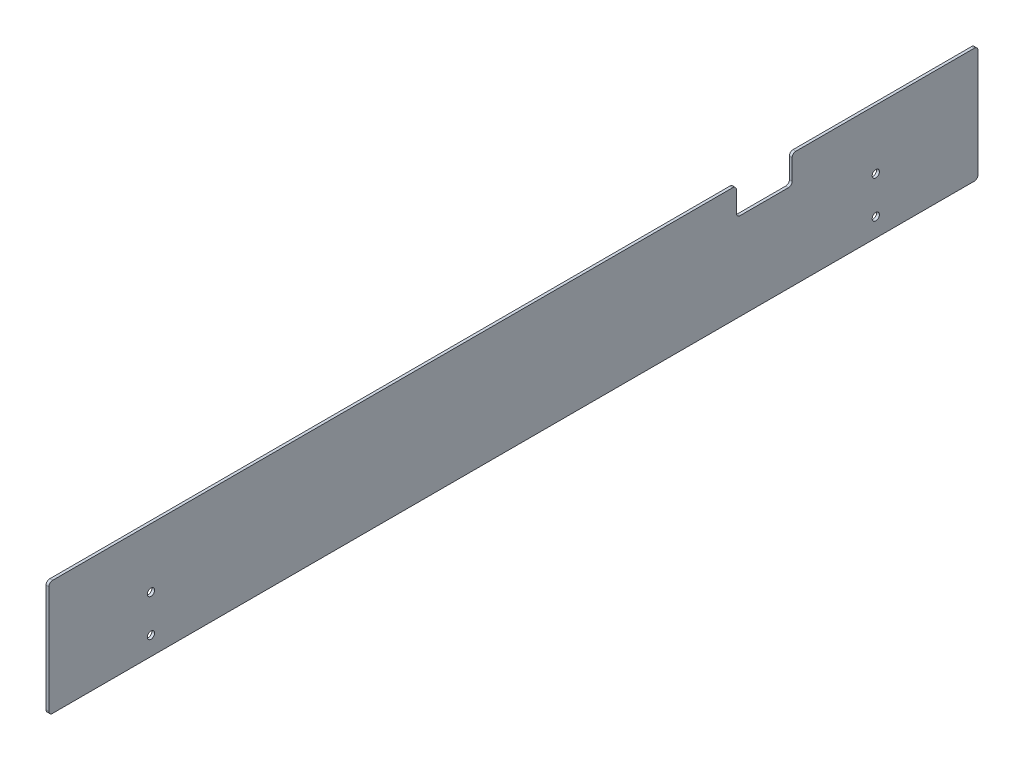
SolidWorks part; units mm, degrees
ref_plane "Front Plane" through (0, 0, 0) normal (0, 0, 1) x (1, 0, 0)
ref_plane "Top Plane" through (0, 0, 0) normal (0, 1, 0) x (1, 0, 0)
ref_plane "Right Plane" through (0, 0, 0) normal (1, 0, 0) x (0, 0, -1)
sketch "Sketch1" plane through (0, 0, 0) normal (1, 0, 0) x (0, 0, -1)
  line L0 (130.0532, -78.2926) -> (230.0532, -78.2926)
  line L1 (-269.9468, -78.2926) -> (100.0532, -78.2926)
  line L2 (-269.9468, -78.2926) -> (-269.9468, -140.2926)
  line L3 (-269.9468, -140.2926) -> (230.0532, -140.2926)
  line L4 (230.0532, -78.2926) -> (230.0532, -140.2926)
  line L6 (130.0532, -78.2926) -> (130.0532, -93.2926)
  line L7 (130.0532, -93.2926) -> (100.0532, -93.2926)
  line L8 (100.0532, -78.2926) -> (100.0532, -93.2926)
  dimension "D1" = 500
  dimension "D2" = 62
  dimension "D3" = 30
  dimension "D4" = 100
  dimension "D5" = 15
extrude "Boss-Extrude1" add sketch "Sketch1" along normal blind 1.5
fillet "Fillet1" radius 2 8 edges at (0.75, -140.2926, -230.0532) (0.75, -140.2926, 269.9468) (0.75, -78.2926, 269.9468) (0.75, -78.2926, -100.0532) (0.75, -93.2926, -100.0532) (0.75, -93.2926, -130.0532) (0.75, -78.2926, -130.0532) (0.75, -78.2926, -230.0532)
sketch "Sketch2" plane through (0, 0, 0) normal (-1, 0, 0) x (0, 0, 1)
  line L0 (-230.0532, -138.2926) -> (-230.0532, -80.2926) construction
  line L1 (267.9468, -140.2926) -> (-228.0532, -140.2926) construction
  line L2 (269.9468, -80.2926) -> (269.9468, -138.2926) construction
  circle A0 centre (-175.0532, -110.2926) radius 1.95
  circle A1 centre (-175.0532, -130.2926) radius 1.95
  circle A2 centre (214.9468, -110.2926) radius 1.95
  circle A3 centre (214.9468, -130.2926) radius 1.95
  dimension "D1" = 55
  dimension "D2" = 20
  dimension "D3" = 10
  dimension "D4" = 55
  dimension "D5" = 20
  dimension "D6" = 10
extrude "Cut-Extrude1" cut sketch "Sketch2" against normal blind 10
